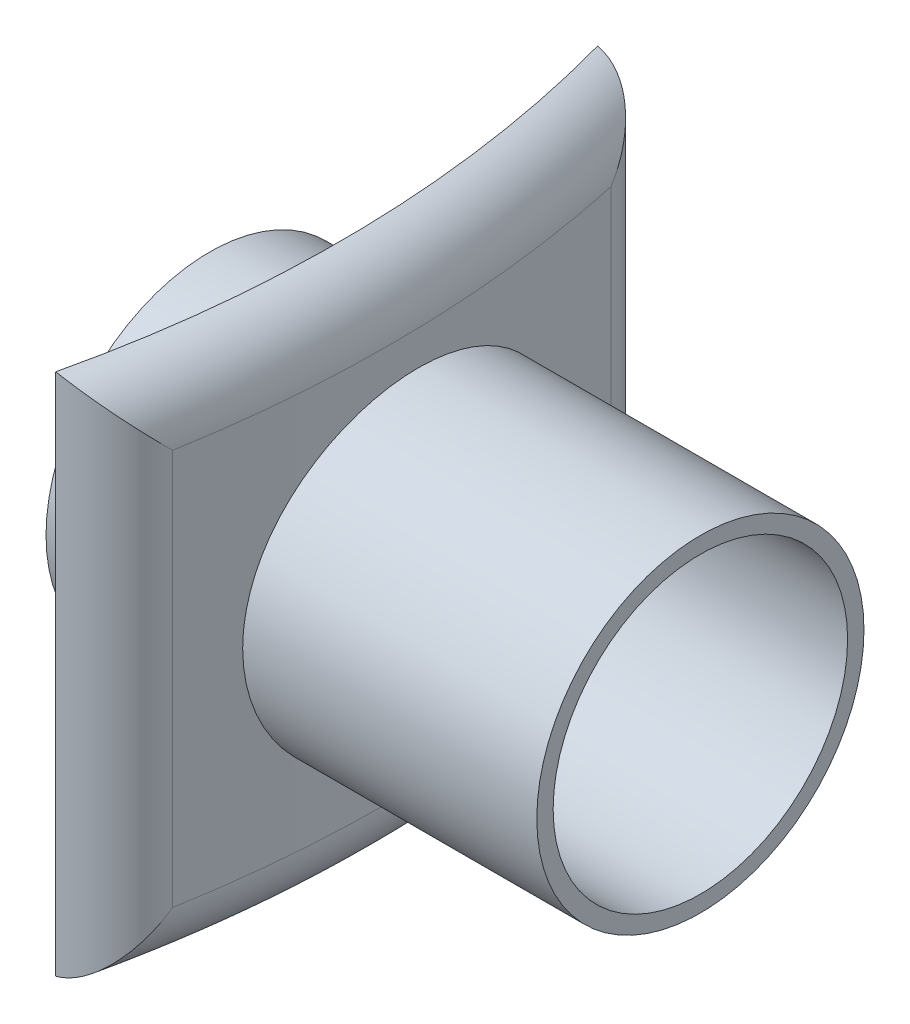
SolidWorks part; units mm, degrees
ref_plane "Front Plane" through (0, 0, 0) normal (0, 0, 1) x (1, 0, 0)
ref_plane "Top Plane" through (0, 0, 0) normal (0, 1, 0) x (1, 0, 0)
ref_plane "Right Plane" through (0, 0, 0) normal (1, 0, 0) x (0, 0, -1)
sketch "Sketch3" plane through (0, 0, 0) normal (1, 0, 0) x (0, 0, -1)
  circle A0 centre (0, 0) radius 5
  circle A1 centre (0, 0) radius 3.3
  dimension "D1" = 10
  dimension "D2" = 6.6
extrude "Boss-Extrude3" add sketch "Sketch3" along normal blind 15 contours A1 | A0 region at (0, 0, 0)
sketch "Sketch6" plane through (0, 0, 0) normal (0, 1, 0) x (1, 0, 0)
  line L1 (3.4775, 8.3808) -> (4.92, 8.9783)
  line L2 (3.8195, -8.5225) -> (5.27, -9.1233)
  arc A0 (3.8195, -8.5225) -> (3.4775, 8.3808) centre (-29.5351, -0.7421) ccw
  arc A1 (5.27, -9.1233) -> (4.92, 8.9783) centre (-29.5351, -0.7421) ccw
  circle A2 centre (-29.5351, -0.7421) radius 34.25 construction
  circle A3 centre (-29.5351, -0.7421) radius 35.8 construction
  dimension "D1" = 1.55
extrude "Boss-Extrude4" add sketch "Sketch6" along normal blind 8 and the other way blind 8 contours L2 A1 L1 A0
sketch "Sketch7" plane through (0, 0, 0) normal (-1, 0, 0) x (0, 0, 1)
  circle A0 centre (0, 0) radius 4.5
  dimension "D1" = 9
extrude "Cut-Extrude1" cut sketch "Sketch7" against normal up to surface (15 mm away) from offset 1 up to face at (15, 0, -5) offset against normal yes
fillet "Fillet2" radius 2 4 edges at (6.2582, 8, 0.05) (4.92, 0, -8.9783) (6.2582, -8, 0.05) (5.27, 0, 9.1233)
